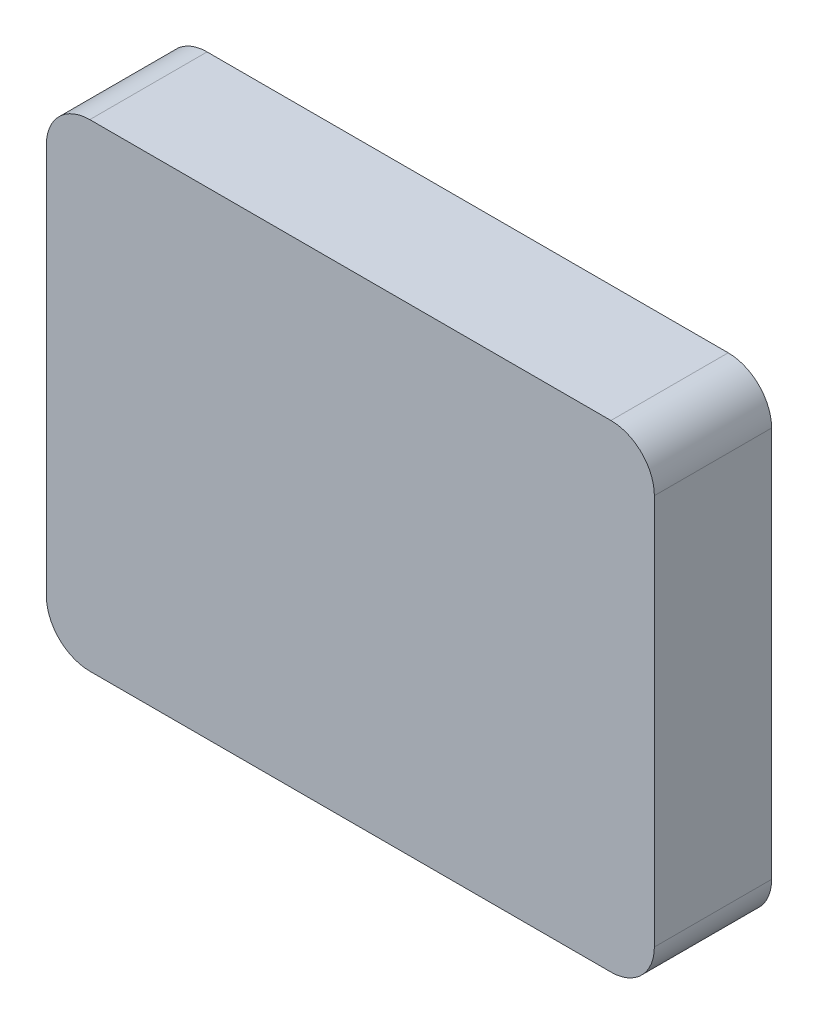
SolidWorks part; units mm, degrees
ref_plane "Front Plane" through (0, 0, 0) normal (0, 0, 1) x (1, 0, 0)
ref_plane "Top Plane" through (0, 0, 0) normal (0, 1, 0) x (1, 0, 0)
ref_plane "Right Plane" through (0, 0, 0) normal (1, 0, 0) x (0, 0, -1)
sketch "Sketch1" plane through (0, 0, 0) normal (0, 0, 1) x (1, 0, 0)
  line L1 (20.0007, 90) -> (-119.9994, 90)
  line L2 (20.0007, 90) -> (20.0007, -20)
  line L3 (20.0007, -20) -> (-119.9994, -20)
  line L4 (-119.9994, 90) -> (-119.9994, -20)
ref_plane "Plane1" through (-99.9994, 0, -1.5) normal (-1, 0, 0) x (0, 0, 1)
extrude "Boss-Extrude1" add sketch "Sketch1" along normal offset from surface (27 mm away) 2 offset beyond the face yes
fillet "Fillet1" radius 10 4 edges at (20.0007, 90, 13.5) (-119.9994, 90, 13.5) (-119.9994, -20, 13.5) (20.0007, -20, 13.5)
sketch "Sketch3" plane through (0, 0, 0) normal (0, 0, -1) x (-1, 0, 0)
  line L8 (109.9994, 80) -> (-10.0007, 80)
  line L9 (-10.0007, 80) -> (-10.0007, -10)
  line L10 (-10.0007, -10) -> (109.9994, -10)
  line L11 (109.9994, -10) -> (109.9994, 80)
  line L12 (106.9994, 80) -> (-7.0006, 80)
  line L13 (-10.0007, 77) -> (-10.0007, -7)
  line L14 (-7.0007, -10) -> (106.9994, -10)
  line L15 (109.9993, -7) -> (109.9993, 77)
  arc A4 (-10.0007, -7) -> (-7.0007, -10) centre (-7.0007, -7) ccw
  arc A5 (106.9994, -10) -> (109.9993, -7) centre (106.9994, -7) ccw
  arc A6 (106.9994, 80) -> (109.9993, 77) centre (106.9994, 77) cw
  arc A7 (-7.0006, 80) -> (-10.0007, 77) centre (-7.0006, 77) ccw
  dimension "D2" = 3
  dimension "D1" = 10
extrude "Cut-Extrude1" cut sketch "Sketch3" against normal offset from surface (25 mm away) 2 up to face at (-49.9993, 35, 27)
sketch "Sketch5" plane through (0, 0, 0) normal (0, 0, -1) x (-1, 0, 0)
  line L12 (-7.0007, -13) -> (106.9994, -13)
  line L13 (112.9993, -7) -> (112.9993, 77)
  line L14 (106.9994, 83) -> (-7.0006, 83)
  line L15 (-13.0007, 77) -> (-13.0007, -7)
  line L16 (-7.0007, -13) -> (106.9994, -13)
  line L17 (112.9993, -7) -> (112.9993, 77)
  line L18 (106.9994, 83) -> (-7.0006, 83)
  line L19 (-13.0007, 77) -> (-13.0007, -7)
  line L24 (-7.0007, -17) -> (106.9994, -17)
  line L25 (116.9994, -7) -> (116.9994, 77)
  line L26 (106.9994, 87) -> (-7.0006, 87)
  line L27 (-17.0007, 77) -> (-17.0007, -7)
  line L28 (-7.0007, -17) -> (106.9994, -17)
  line L29 (116.9994, -7) -> (116.9994, 77)
  line L30 (106.9994, 87) -> (-7.0006, 87)
  line L31 (-17.0007, 77) -> (-17.0007, -7)
  arc A12 (-13.0007, -7) -> (-7.0007, -13) centre (-7.0007, -7) ccw
  arc A13 (106.9994, -13) -> (112.9993, -7) centre (106.9994, -7) ccw
  arc A14 (112.9993, 77) -> (106.9994, 83) centre (106.9994, 77) ccw
  arc A15 (-7.0006, 83) -> (-13.0007, 77) centre (-7.0006, 77) ccw
  arc A16 (-13.0007, -7) -> (-7.0007, -13) centre (-7.0007, -7) ccw
  arc A17 (106.9994, -13) -> (112.9993, -7) centre (106.9994, -7) ccw
  arc A18 (112.9993, 77) -> (106.9994, 83) centre (106.9994, 77) ccw
  arc A19 (-7.0006, 83) -> (-13.0007, 77) centre (-7.0006, 77) ccw
  arc A24 (-17.0007, -7) -> (-7.0007, -17) centre (-7.0007, -7) ccw
  arc A25 (106.9994, -17) -> (116.9994, -7) centre (106.9994, -7) ccw
  arc A26 (116.9994, 77) -> (106.9994, 87) centre (106.9994, 77) ccw
  arc A27 (-7.0006, 87) -> (-17.0007, 77) centre (-7.0006, 77) ccw
  arc A28 (-17.0007, -7) -> (-7.0007, -17) centre (-7.0007, -7) ccw
  arc A29 (106.9994, -17) -> (116.9994, -7) centre (106.9994, -7) ccw
  arc A30 (116.9994, 77) -> (106.9994, 87) centre (106.9994, 77) ccw
  arc A31 (-7.0006, 87) -> (-17.0007, 77) centre (-7.0006, 77) ccw
  dimension "D1" = 3
  dimension "D2" = 7
extrude "Cut-Extrude2" cut sketch "Sketch5" against normal blind 2
sketch "Sketch6" plane through (0, 0, 25) normal (0, 0, -1) x (-1, 0, 0)
  line L0 (0.8629, 70.2252) -> (0.8629, 80)
  line L1 (106.9994, 80) -> (-7.0006, 80) construction
  line L2 (-6.1371, 63.2252) -> (-10.0007, 63.2252)
  line L3 (-10.0007, 77) -> (-10.0007, -7) construction
  line L4 (82.1129, 70.2252) -> (82.1129, 80)
  line L5 (96.1129, 70.2252) -> (96.1129, 80)
  line L6 (-10.0006, 12.4537) -> (-10.0006, -1.5463)
  line L7 (0.8629, 80) -> (-7.0006, 80)
  line L10 (-6.1384, 12.4537) -> (-10.0006, 12.4537)
  line L11 (-10.0006, -1.5463) -> (-10.0007, -7)
  line L13 (86.1553, 12.7962) -> (86.1553, 6.1922) construction
  line L14 (-7.0007, -10) -> (106.9994, -10)
  line L15 (109.9993, -7) -> (109.9993, 77)
  line L16 (106.9994, 80) -> (-7.0006, 80)
  line L17 (-10.0007, 77) -> (-10.0007, -7)
  line L20 (96.1129, 80) -> (82.1129, 80)
  line L21 (-10.0007, 77) -> (-10.0007, 63.2252)
  line L22 (-4.0007, -10) -> (-7.0007, -10)
  line L24 (87.1553, 12.1759) -> (87.1553, -1.2655)
  line L25 (106.9994, 74) -> (109.9993, 74)
  line L26 (109.9993, -7) -> (109.9993, 77) construction
  line L28 (103.9994, 77) -> (103.9994, 80)
  line L29 (103.9994, -7) -> (103.9994, -10)
  line L30 (-7.0007, -10) -> (106.9994, -10) construction
  line L31 (106.9994, -4) -> (109.9993, -4)
  line L32 (103.9994, -10) -> (106.9994, -10)
  line L33 (109.9993, -7) -> (109.9993, -4)
  line L37 (103.9994, 80) -> (106.9994, 80)
  line L38 (109.9993, 77) -> (109.9993, 74)
  line L39 (-4.0007, -10) -> (-4.0007, -1.2119)
  arc A0 (-6.1371, 63.2252) -> (0.8629, 70.2252) centre (-6.1371, 70.2252) ccw
  arc A1 (82.1129, 70.2252) -> (96.1129, 70.2252) centre (89.1129, 70.2252) ccw
  arc A2 (103.9994, 77) -> (106.9994, 74) centre (106.9994, 77) ccw
  arc A3 (106.9994, -4) -> (103.9994, -7) centre (106.9994, -7) ccw
  arc A5 (106.9994, -10) -> (109.9993, -7) centre (106.9994, -7) ccw
  arc A8 (87.1553, -1.2655) -> (87.1553, 12.1759) centre (89.1129, 5.4552) ccw
  arc A9 (-4.0007, -1.2119) -> (-6.1384, 12.4537) centre (-6.1384, 5.4537) ccw
  arc A10 (-10.0007, -7) -> (-7.0007, -10) centre (-7.0007, -7) ccw
  arc A11 (106.9994, -10) -> (109.9993, -7) centre (106.9994, -7) ccw
  arc A12 (109.9993, 77) -> (106.9994, 80) centre (106.9994, 77) ccw
  arc A13 (-7.0006, 80) -> (-10.0007, 77) centre (-7.0006, 77) ccw
  arc A17 (-7.0006, 80) -> (-10.0007, 77) centre (-7.0006, 77) ccw
  arc A18 (109.9993, 77) -> (106.9994, 80) centre (106.9994, 77) ccw construction
  arc A19 (109.9993, 77) -> (106.9994, 80) centre (106.9994, 77) ccw
  arc A20 (-10.0007, -7) -> (-7.0007, -10) centre (-7.0007, -7) ccw construction
  arc A21 (-10.0007, -7) -> (-7.0007, -10) centre (-7.0007, -7) ccw
  dimension "D3" = 14
  dimension "D2" = 14
  dimension "D4" = 14
  dimension "D6" = 14
  dimension "D7" = 1
  dimension "D1" = 0
extrude "Boss-Extrude2" add sketch "Sketch6" along normal up to surface (25 mm away)
fillet "Fillet2" radius 3 6 edges at (10.0007, 12.4537, 12.5) (10.0007, 63.2252, 12.5) (-0.8629, 80, 12.5) (-82.1129, 80, 12.5) (-96.1129, 80, 12.5) (4.0007, -1.2119, 12.5)
hole_wizard "M3 Clearance Hole1" positions "Sketch8" profile "Sketch9" hole size "M3" standard "ISO"
sketch "Sketch8" plane through (0, 0, 0) normal (0, 0, -1) x (-1, 0, 0)
  point P0 (-6.1371, 70.2252)
  point P3 (89.1129, 70.2252)
  point P6 (89.1129, 5.4552)
  point P9 (-6.1384, 5.4537)
  point P13 (-7.0006, 77)
  point P16 (106.9994, 77)
  point P19 (106.9994, -7)
  point P22 (-7.0007, -7)
sketch "Sketch9" plane through (6.1371, 70.2252, 0) normal (1, 0, 0) x (0, 1, 0)
  line L0 (0, 0) -> (0, 16.0215)
  line L1 (0, 16.0215) -> (1.7, 15)
  line L2 (1.7, 15) -> (1.7, 0)
  line L5 (1.7, 0) -> (0, 0)
  line L10 (0, 16.0215) -> (-1.7, 15) construction
  line L11 (0, -6.35) -> (0, 107.95) construction
  dimension "Hole Dia." = 3.4
  dimension "Hole Depth" = 15
  dimension "Drill Angle" = 118
fillet "Fillet3" radius 3 5 edges at (-109.9993, 74, 12.5) (-103.9994, 80, 12.5) (-109.9993, -4, 12.5) (-103.9994, -10, 12.5) (4.0007, -10, 12.5)
ref_plane "Plane2" through (-106.9994, -4, 0) normal (1, 0, 0) x (0, 0, -1)
equation "\"D2@Sketch6\"=\"D3@Sketch6\""
equation "\"D6@Sketch6\"=\"D3@Sketch6\""
